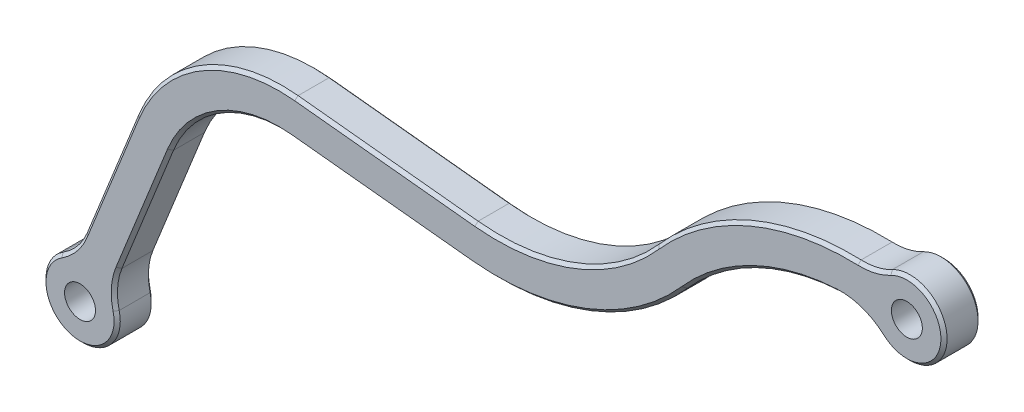
SolidWorks part; units mm, degrees
note: The reader was unsure of these and kept them because the rebuilt part matched: shared geometry of "Sketch1<3>".
other "DetailItem1"
other "DetailItem2"
material "Titanium Ti-8Mn, Annealed"
ref_plane "Спереди" through (0, 0, 0) normal (0, 0, 1) x (1, 0, 0)
ref_plane "Сверху" through (0, 0, 0) normal (0, 1, 0) x (1, 0, 0)
ref_plane "Справа" through (0, 0, 0) normal (1, 0, 0) x (0, 0, -1)
other "Configuration Table"
sketch "Sketch1" plane through (0, 0, 0) normal (0, 0, 1) x (1, 0, 0)
  line L0 (32.4057, 20.4925) -> (17.8642, 22.0056)
  line L1 (30.9283, 23.6624) -> (21.4794, 24.6456) construction
  line L2 (6.5582, 15.1948) -> (0.6537, 0.5285)
  circle A0 centre (0.6537, 0.5285) radius 3 construction
  circle A1 centre (0.6537, 0.5285) radius 3
  arc A3 (70.3356, 33.4669) -> (64.5425, 31.9047) centre (67.439, 32.6858) ccw construction
  circle A4 centre (67.439, 32.6858) radius 3
  arc A5 (32.4057, 20.4925) -> (48.3243, 26.7177) centre (34.3343, 39.0265) ccw
  arc A6 (48.3243, 26.7177) -> (67.439, 32.6858) centre (62.786, 13.994) cw
  arc A7 (17.8642, 22.0056) -> (6.5582, 15.1948) centre (16.7294, 11.1) ccw
  arc A9 (27.3821, 20.9871) -> (24.3988, 21.2975) centre (25.8934, 21.1702) ccw construction
extrude "Extrude-Thin1" add sketch "Sketch1" along normal blind 3 thin contours A5 L0 | L0 A7 L2
extrude "Boss-Extrude1" add sketch "Sketch1<3>" along normal through all
sketch "Sketch1<3>" plane through (0, 0, 0) normal (0, 0, 1) x (1, 0, 0) same geometry as "Sketch1"
fillet "Fillet1" radius 5 4 edges at (3.0154, 2.3784, 1.5) (0.2325, 3.4988, 1.5) (64.6194, 31.6613, 1.5) (65.1471, 34.6215, 1.5)
hole_wizard "Ø2.5mm Dowel Hole1" positions "Sketch2" profile "Sketch3" hole size "Ø2.5" standard "ISO" end condition through all
sketch "Sketch2" plane through (0, 0, 3) normal (0, 0, 1) x (1, 0, 0)
  arc A0 (65.433, 30.4551) -> (66.0248, 35.3315) centre (67.439, 32.6858) ccw construction
  arc A1 (65.433, 30.4551) -> (66.0248, 35.3315) centre (67.439, 32.6858) ccw
  point P0 (67.439, 32.6858)
  point P2 (0.6537, 0.5285)
sketch "Sketch3" plane through (67.439, 32.6858, 3) normal (1, 0, 0) x (0, -1, 0)
  line L0 (0, 0) -> (0, 3)
  line L1 (0, 3) -> (1.25, 3)
  line L2 (1.25, 3) -> (1.25, 0)
  line L5 (1.25, 0) -> (0, 0)
  line L11 (0, -6.35) -> (0, 107.95) construction
  dimension "Thru Hole Dia." = 2.5
  dimension "Thru Hole Depth" = 3
chamfer "Chamfer1" distance 0.25 angle 45 32 edges at (41.6672, 20.2753, 0) (41.6672, 20.2753, 3) (55.0295, 29.9731, 0) (55.0295, 29.9731, 3) (24.9797, 19.7571, 0) (24.9797, 19.7571, 3) (63.7521, 31.4528, 0) (63.7521, 31.4528, 3) (11.8456, 19.2071, 0) (11.8456, 19.2071, 3) (70.4172, 32.3244, 3) (70.4172, 32.3244, 0) (5.8683, 9.4646, 3) (5.8683, 9.4646, 0) (64.7995, 34.8709, 0) (64.7995, 34.8709, 3) (3.4379, 2.7848, 3) (3.4379, 2.7848, 0) (54.5576, 33.0561, 3) (54.5576, 33.0561, 0) (-0.4667, -2.2544, 0) (-0.4667, -2.2544, 3) (40.5746, 23.0692, 0) (40.5746, 23.0692, 3) (0.2094, 4.0845, 3) (0.2094, 4.0845, 0) (25.2902, 22.741, 0) (25.2902, 22.741, 3) (3.0853, 10.585, 0) (3.0853, 10.585, 3) (10.2975, 21.7769, 0) (10.2975, 21.7769, 3)
